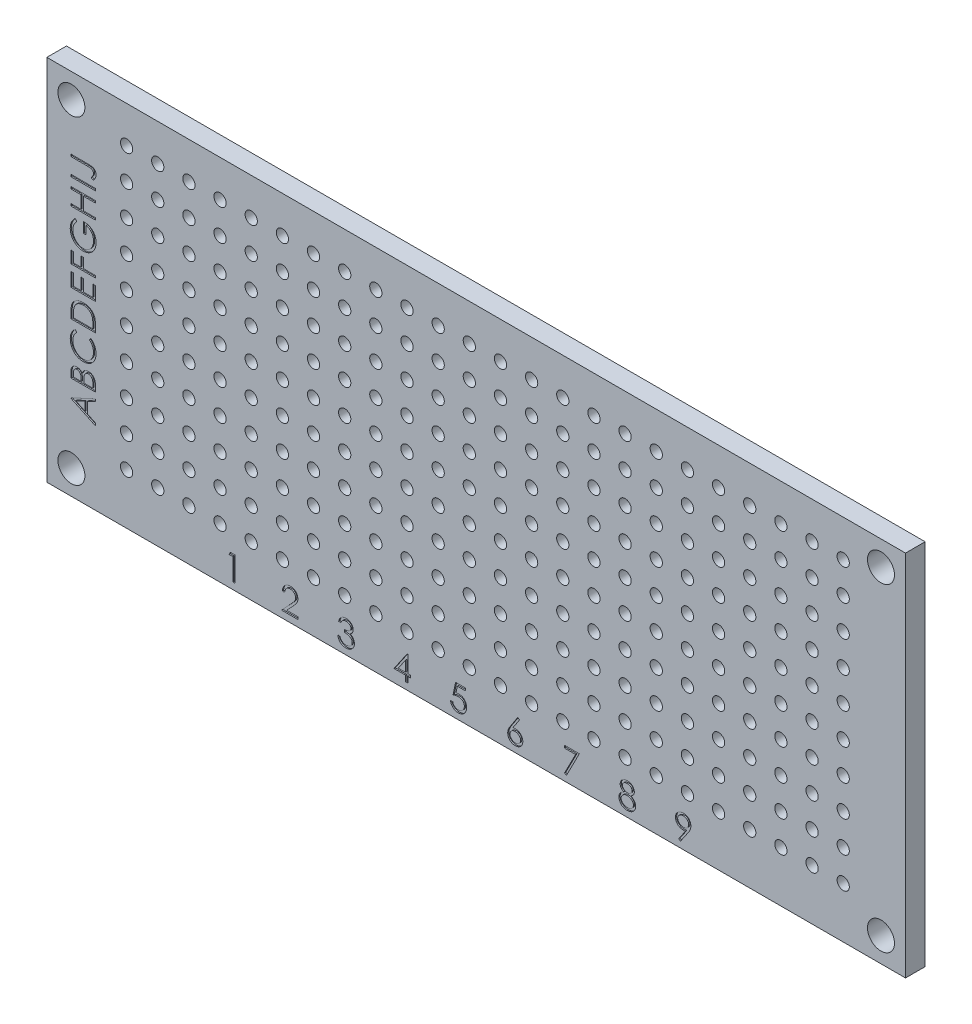
SolidWorks part; units mm, degrees
ref_plane "Front Plane" through (0, 0, 0) normal (0, 0, 1) x (1, 0, 0)
ref_plane "Top Plane" through (0, 0, 0) normal (0, 1, 0) x (1, 0, 0)
ref_plane "Right Plane" through (0, 0, 0) normal (1, 0, 0) x (0, 0, -1)
sketch "Skica1" plane through (0, 0, 0) normal (0, 0, 1) x (1, 0, 0)
  line L0 (-33, 13) -> (-33, -13) construction
  line L1 (-35, 15) -> (35, 15)
  line L2 (-35, 15) -> (-35, -15)
  line L3 (-35, -15) -> (35, -15)
  line L4 (35, 15) -> (35, -15)
  line L5 (-35, 15) -> (35, -15) construction
  line L6 (-35, -15) -> (35, 15) construction
  line L7 (-33, -13) -> (33, -13) construction
  line L8 (33, 13) -> (33, -13) construction
  line L9 (-33, 13) -> (33, 13) construction
  circle A0 centre (-33, 13) radius 1.1
  circle A1 centre (33, 13) radius 1.1
  circle A2 centre (33, -13) radius 1.1
  circle A3 centre (-33, -13) radius 1.1
  point P0 (0, 0)
  dimension "D4" = 2.2
  dimension "D5" = 2.2
  dimension "D8" = 2.2
  dimension "D9" = 2.2
  dimension "D1" = 30
  dimension "D2" = 70
  dimension "D6" = 66
  dimension "D7" = 0.9
  dimension "D3" = 2
extrude "Přidat vysunutím1" add sketch "Skica1" along normal blind 1.6
sketch "Skica2" plane through (0, 0, 1.6) normal (0, 0, 1) x (1, 0, 0)
  line L0 (0, 0) -> (0, -9.2979) construction
  line L1 (0, 0) -> (-8.7573, 0) construction
  line L2 (-28.5, 12) -> (-25.96, 12) construction
  line L3 (-28.5, 12) -> (-28.5, 9.46) construction
  line L4 (-35, -15) -> (35, -15) construction
  line L5 (35, 15) -> (-35, 15) construction
  line L6 (-35, 15) -> (-35, -15) construction
  line L7 (35, -15) -> (35, 15) construction
  circle A0 centre (-28.5, 12) radius 0.5
  circle A1 centre (-25.96, 12) radius 0.5
  circle A2 centre (-23.42, 12) radius 0.5
  circle A3 centre (-20.88, 12) radius 0.5
  circle A4 centre (-18.34, 12) radius 0.5
  circle A5 centre (-15.8, 12) radius 0.5
  circle A6 centre (-13.26, 12) radius 0.5
  circle A7 centre (-10.72, 12) radius 0.5
  circle A8 centre (-8.18, 12) radius 0.5
  circle A9 centre (-5.64, 12) radius 0.5
  circle A10 centre (-3.1, 12) radius 0.5
  circle A11 centre (-0.56, 12) radius 0.5
  circle A12 centre (1.98, 12) radius 0.5
  circle A13 centre (4.52, 12) radius 0.5
  circle A14 centre (7.06, 12) radius 0.5
  circle A15 centre (9.6, 12) radius 0.5
  circle A16 centre (12.14, 12) radius 0.5
  circle A17 centre (14.68, 12) radius 0.5
  circle A18 centre (17.22, 12) radius 0.5
  circle A19 centre (19.76, 12) radius 0.5
  circle A20 centre (22.3, 12) radius 0.5
  circle A21 centre (24.84, 12) radius 0.5
  circle A22 centre (27.38, 12) radius 0.5
  circle A23 centre (29.92, 12) radius 0.5
  circle A24 centre (-25.96, 9.46) radius 0.5
  circle A25 centre (-23.42, 9.46) radius 0.5
  circle A26 centre (-20.88, 9.46) radius 0.5
  circle A27 centre (-18.34, 9.46) radius 0.5
  circle A28 centre (-15.8, 9.46) radius 0.5
  circle A29 centre (-13.26, 9.46) radius 0.5
  circle A30 centre (-10.72, 9.46) radius 0.5
  circle A31 centre (-8.18, 9.46) radius 0.5
  circle A32 centre (-5.64, 9.46) radius 0.5
  circle A33 centre (-3.1, 9.46) radius 0.5
  circle A34 centre (-0.56, 9.46) radius 0.5
  circle A35 centre (1.98, 9.46) radius 0.5
  circle A36 centre (4.52, 9.46) radius 0.5
  circle A37 centre (7.06, 9.46) radius 0.5
  circle A38 centre (9.6, 9.46) radius 0.5
  circle A39 centre (12.14, 9.46) radius 0.5
  circle A40 centre (14.68, 9.46) radius 0.5
  circle A41 centre (17.22, 9.46) radius 0.5
  circle A42 centre (19.76, 9.46) radius 0.5
  circle A43 centre (22.3, 9.46) radius 0.5
  circle A44 centre (24.84, 9.46) radius 0.5
  circle A45 centre (27.38, 9.46) radius 0.5
  circle A46 centre (29.92, 9.46) radius 0.5
  circle A47 centre (-25.96, 6.92) radius 0.5
  circle A48 centre (-23.42, 6.92) radius 0.5
  circle A49 centre (-20.88, 6.92) radius 0.5
  circle A50 centre (-18.34, 6.92) radius 0.5
  circle A51 centre (-15.8, 6.92) radius 0.5
  circle A52 centre (-13.26, 6.92) radius 0.5
  circle A53 centre (-10.72, 6.92) radius 0.5
  circle A54 centre (-8.18, 6.92) radius 0.5
  circle A55 centre (-5.64, 6.92) radius 0.5
  circle A56 centre (-3.1, 6.92) radius 0.5
  circle A57 centre (-0.56, 6.92) radius 0.5
  circle A58 centre (1.98, 6.92) radius 0.5
  circle A59 centre (4.52, 6.92) radius 0.5
  circle A60 centre (7.06, 6.92) radius 0.5
  circle A61 centre (9.6, 6.92) radius 0.5
  circle A62 centre (12.14, 6.92) radius 0.5
  circle A63 centre (14.68, 6.92) radius 0.5
  circle A64 centre (17.22, 6.92) radius 0.5
  circle A65 centre (19.76, 6.92) radius 0.5
  circle A66 centre (22.3, 6.92) radius 0.5
  circle A67 centre (24.84, 6.92) radius 0.5
  circle A68 centre (27.38, 6.92) radius 0.5
  circle A69 centre (29.92, 6.92) radius 0.5
  circle A70 centre (-25.96, 4.38) radius 0.5
  circle A71 centre (-23.42, 4.38) radius 0.5
  circle A72 centre (-20.88, 4.38) radius 0.5
  circle A73 centre (-18.34, 4.38) radius 0.5
  circle A74 centre (-15.8, 4.38) radius 0.5
  circle A75 centre (-13.26, 4.38) radius 0.5
  circle A76 centre (-10.72, 4.38) radius 0.5
  circle A77 centre (-8.18, 4.38) radius 0.5
  circle A78 centre (-5.64, 4.38) radius 0.5
  circle A79 centre (-3.1, 4.38) radius 0.5
  circle A80 centre (-0.56, 4.38) radius 0.5
  circle A81 centre (1.98, 4.38) radius 0.5
  circle A82 centre (4.52, 4.38) radius 0.5
  circle A83 centre (7.06, 4.38) radius 0.5
  circle A84 centre (9.6, 4.38) radius 0.5
  circle A85 centre (12.14, 4.38) radius 0.5
  circle A86 centre (14.68, 4.38) radius 0.5
  circle A87 centre (17.22, 4.38) radius 0.5
  circle A88 centre (19.76, 4.38) radius 0.5
  circle A89 centre (22.3, 4.38) radius 0.5
  circle A90 centre (24.84, 4.38) radius 0.5
  circle A91 centre (27.38, 4.38) radius 0.5
  circle A92 centre (29.92, 4.38) radius 0.5
  circle A93 centre (-25.96, 1.84) radius 0.5
  circle A94 centre (-23.42, 1.84) radius 0.5
  circle A95 centre (-20.88, 1.84) radius 0.5
  circle A96 centre (-18.34, 1.84) radius 0.5
  circle A97 centre (-15.8, 1.84) radius 0.5
  circle A98 centre (-13.26, 1.84) radius 0.5
  circle A99 centre (-10.72, 1.84) radius 0.5
  circle A100 centre (-8.18, 1.84) radius 0.5
  circle A101 centre (-5.64, 1.84) radius 0.5
  circle A102 centre (-3.1, 1.84) radius 0.5
  circle A103 centre (-0.56, 1.84) radius 0.5
  circle A104 centre (1.98, 1.84) radius 0.5
  circle A105 centre (4.52, 1.84) radius 0.5
  circle A106 centre (7.06, 1.84) radius 0.5
  circle A107 centre (9.6, 1.84) radius 0.5
  circle A108 centre (12.14, 1.84) radius 0.5
  circle A109 centre (14.68, 1.84) radius 0.5
  circle A110 centre (17.22, 1.84) radius 0.5
  circle A111 centre (19.76, 1.84) radius 0.5
  circle A112 centre (22.3, 1.84) radius 0.5
  circle A113 centre (24.84, 1.84) radius 0.5
  circle A114 centre (27.38, 1.84) radius 0.5
  circle A115 centre (29.92, 1.84) radius 0.5
  circle A116 centre (-25.96, -0.7) radius 0.5
  circle A117 centre (-23.42, -0.7) radius 0.5
  circle A118 centre (-20.88, -0.7) radius 0.5
  circle A119 centre (-18.34, -0.7) radius 0.5
  circle A120 centre (-15.8, -0.7) radius 0.5
  circle A121 centre (-13.26, -0.7) radius 0.5
  circle A122 centre (-10.72, -0.7) radius 0.5
  circle A123 centre (-8.18, -0.7) radius 0.5
  circle A124 centre (-5.64, -0.7) radius 0.5
  circle A125 centre (-3.1, -0.7) radius 0.5
  circle A126 centre (-0.56, -0.7) radius 0.5
  circle A127 centre (1.98, -0.7) radius 0.5
  circle A128 centre (4.52, -0.7) radius 0.5
  circle A129 centre (7.06, -0.7) radius 0.5
  circle A130 centre (9.6, -0.7) radius 0.5
  circle A131 centre (12.14, -0.7) radius 0.5
  circle A132 centre (14.68, -0.7) radius 0.5
  circle A133 centre (17.22, -0.7) radius 0.5
  circle A134 centre (19.76, -0.7) radius 0.5
  circle A135 centre (22.3, -0.7) radius 0.5
  circle A136 centre (24.84, -0.7) radius 0.5
  circle A137 centre (27.38, -0.7) radius 0.5
  circle A138 centre (29.92, -0.7) radius 0.5
  circle A139 centre (-25.96, -3.24) radius 0.5
  circle A140 centre (-23.42, -3.24) radius 0.5
  circle A141 centre (-20.88, -3.24) radius 0.5
  circle A142 centre (-18.34, -3.24) radius 0.5
  circle A143 centre (-15.8, -3.24) radius 0.5
  circle A144 centre (-13.26, -3.24) radius 0.5
  circle A145 centre (-10.72, -3.24) radius 0.5
  circle A146 centre (-8.18, -3.24) radius 0.5
  circle A147 centre (-5.64, -3.24) radius 0.5
  circle A148 centre (-3.1, -3.24) radius 0.5
  circle A149 centre (-0.56, -3.24) radius 0.5
  circle A150 centre (1.98, -3.24) radius 0.5
  circle A151 centre (4.52, -3.24) radius 0.5
  circle A152 centre (7.06, -3.24) radius 0.5
  circle A153 centre (9.6, -3.24) radius 0.5
  circle A154 centre (12.14, -3.24) radius 0.5
  circle A155 centre (14.68, -3.24) radius 0.5
  circle A156 centre (17.22, -3.24) radius 0.5
  circle A157 centre (19.76, -3.24) radius 0.5
  circle A158 centre (22.3, -3.24) radius 0.5
  circle A159 centre (24.84, -3.24) radius 0.5
  circle A160 centre (27.38, -3.24) radius 0.5
  circle A161 centre (29.92, -3.24) radius 0.5
  circle A162 centre (-25.96, -5.78) radius 0.5
  circle A163 centre (-23.42, -5.78) radius 0.5
  circle A164 centre (-20.88, -5.78) radius 0.5
  circle A165 centre (-18.34, -5.78) radius 0.5
  circle A166 centre (-15.8, -5.78) radius 0.5
  circle A167 centre (-13.26, -5.78) radius 0.5
  circle A168 centre (-10.72, -5.78) radius 0.5
  circle A169 centre (-8.18, -5.78) radius 0.5
  circle A170 centre (-5.64, -5.78) radius 0.5
  circle A171 centre (-3.1, -5.78) radius 0.5
  circle A172 centre (-0.56, -5.78) radius 0.5
  circle A173 centre (1.98, -5.78) radius 0.5
  circle A174 centre (4.52, -5.78) radius 0.5
  circle A175 centre (7.06, -5.78) radius 0.5
  circle A176 centre (9.6, -5.78) radius 0.5
  circle A177 centre (12.14, -5.78) radius 0.5
  circle A178 centre (14.68, -5.78) radius 0.5
  circle A179 centre (17.22, -5.78) radius 0.5
  circle A180 centre (19.76, -5.78) radius 0.5
  circle A181 centre (22.3, -5.78) radius 0.5
  circle A182 centre (24.84, -5.78) radius 0.5
  circle A183 centre (27.38, -5.78) radius 0.5
  circle A184 centre (29.92, -5.78) radius 0.5
  circle A185 centre (-25.96, -8.32) radius 0.5
  circle A186 centre (-23.42, -8.32) radius 0.5
  circle A187 centre (-20.88, -8.32) radius 0.5
  circle A188 centre (-18.34, -8.32) radius 0.5
  circle A189 centre (-15.8, -8.32) radius 0.5
  circle A190 centre (-13.26, -8.32) radius 0.5
  circle A191 centre (-10.72, -8.32) radius 0.5
  circle A192 centre (-8.18, -8.32) radius 0.5
  circle A193 centre (-5.64, -8.32) radius 0.5
  circle A194 centre (-3.1, -8.32) radius 0.5
  circle A195 centre (-0.56, -8.32) radius 0.5
  circle A196 centre (1.98, -8.32) radius 0.5
  circle A197 centre (4.52, -8.32) radius 0.5
  circle A198 centre (7.06, -8.32) radius 0.5
  circle A199 centre (9.6, -8.32) radius 0.5
  circle A200 centre (12.14, -8.32) radius 0.5
  circle A201 centre (14.68, -8.32) radius 0.5
  circle A202 centre (17.22, -8.32) radius 0.5
  circle A203 centre (19.76, -8.32) radius 0.5
  circle A204 centre (22.3, -8.32) radius 0.5
  circle A205 centre (24.84, -8.32) radius 0.5
  circle A206 centre (27.38, -8.32) radius 0.5
  circle A207 centre (29.92, -8.32) radius 0.5
  circle A208 centre (-25.96, -10.86) radius 0.5
  circle A209 centre (-23.42, -10.86) radius 0.5
  circle A210 centre (-20.88, -10.86) radius 0.5
  circle A211 centre (-18.34, -10.86) radius 0.5
  circle A212 centre (-15.8, -10.86) radius 0.5
  circle A213 centre (-13.26, -10.86) radius 0.5
  circle A214 centre (-10.72, -10.86) radius 0.5
  circle A215 centre (-8.18, -10.86) radius 0.5
  circle A216 centre (-5.64, -10.86) radius 0.5
  circle A217 centre (-3.1, -10.86) radius 0.5
  circle A218 centre (-0.56, -10.86) radius 0.5
  circle A219 centre (1.98, -10.86) radius 0.5
  circle A220 centre (4.52, -10.86) radius 0.5
  circle A221 centre (7.06, -10.86) radius 0.5
  circle A222 centre (9.6, -10.86) radius 0.5
  circle A223 centre (12.14, -10.86) radius 0.5
  circle A224 centre (14.68, -10.86) radius 0.5
  circle A225 centre (17.22, -10.86) radius 0.5
  circle A226 centre (19.76, -10.86) radius 0.5
  circle A227 centre (22.3, -10.86) radius 0.5
  circle A228 centre (24.84, -10.86) radius 0.5
  circle A229 centre (27.38, -10.86) radius 0.5
  circle A230 centre (29.92, -10.86) radius 0.5
  circle A231 centre (-28.5, 9.46) radius 0.5
  circle A232 centre (-28.5, 6.92) radius 0.5
  circle A233 centre (-28.5, 4.38) radius 0.5
  circle A234 centre (-28.5, 1.84) radius 0.5
  circle A235 centre (-28.5, -0.7) radius 0.5
  circle A236 centre (-28.5, -3.24) radius 0.5
  circle A237 centre (-28.5, -5.78) radius 0.5
  circle A238 centre (-28.5, -8.32) radius 0.5
  circle A239 centre (-28.5, -10.86) radius 0.5
  dimension "D1" = 1
  dimension "D2" = 28.5
  dimension "D3" = 12
  dimension "D6" = 2.54
  dimension "D7" = 2.54
  dimension "D8" = 4.14
  dimension "D9" = 3
  dimension "D10" = 6.5
  dimension "D11" = 5.08
  dimension "D4" = 24
  dimension "D5" = 10
extrude "Odebrat vysunutím1" cut sketch "Skica2" against normal blind 1.6
sketch "Skica3" plane through (0, 0, 1.6) normal (0, 0, 1) x (1, 0, 0)
  line L0 (-18.34, 9.46) -> (-10.72, 4.38) construction
  line L1 (-28.5, 1.84) -> (-20.88, -3.24) construction
  line L2 (-18.34, -5.78) -> (-10.72, -10.86) construction
  line L3 (-8.18, 1.84) -> (-0.56, -3.24) construction
  line L4 (17.22, -5.78) -> (9.6, -0.7) construction
  line L5 (22.3, -0.7) -> (29.92, -5.78) construction
  circle A0 centre (-10.72, 4.38) radius 0.5 construction
  circle A1 centre (-18.34, 9.46) radius 0.5 construction
  circle A2 centre (-8.18, 1.84) radius 0.5 construction
  circle A3 centre (-0.56, -3.24) radius 0.5 construction
  circle A4 centre (9.6, -0.7) radius 0.5 construction
  circle A5 centre (17.22, -5.78) radius 0.5 construction
  circle A6 centre (22.3, -0.7) radius 0.5 construction
  circle A7 centre (29.92, -5.78) radius 0.5 construction
  point P24 (-14.53, 6.92)
  point P25 (-24.69, -0.7)
  point P28 (-14.53, -8.32)
  point P29 (-4.37, -0.7)
  point P30 (13.41, -3.24)
  point P31 (26.11, -3.24)
sketch "Skica4" plane through (0, 0, 1.6) normal (0, 0, 1) x (1, 0, 0)
  line L0 (-20.5324, -14.4593) -> (21.133, -14.4593) construction
  line L1 (-31.0426, 9.4138) -> (-31.0426, -10.6306) construction
  text T0 "123456789" font "Century Gothic" height 2
  text T1 "ABCDEFGHIJ" font "Century Gothic" height 2
  point P5 (0, 0)
  point P6 (-33.9705, -10.6306)
extrude "Odebrat vysunutím2" cut sketch "Skica4" against normal blind 0.1
